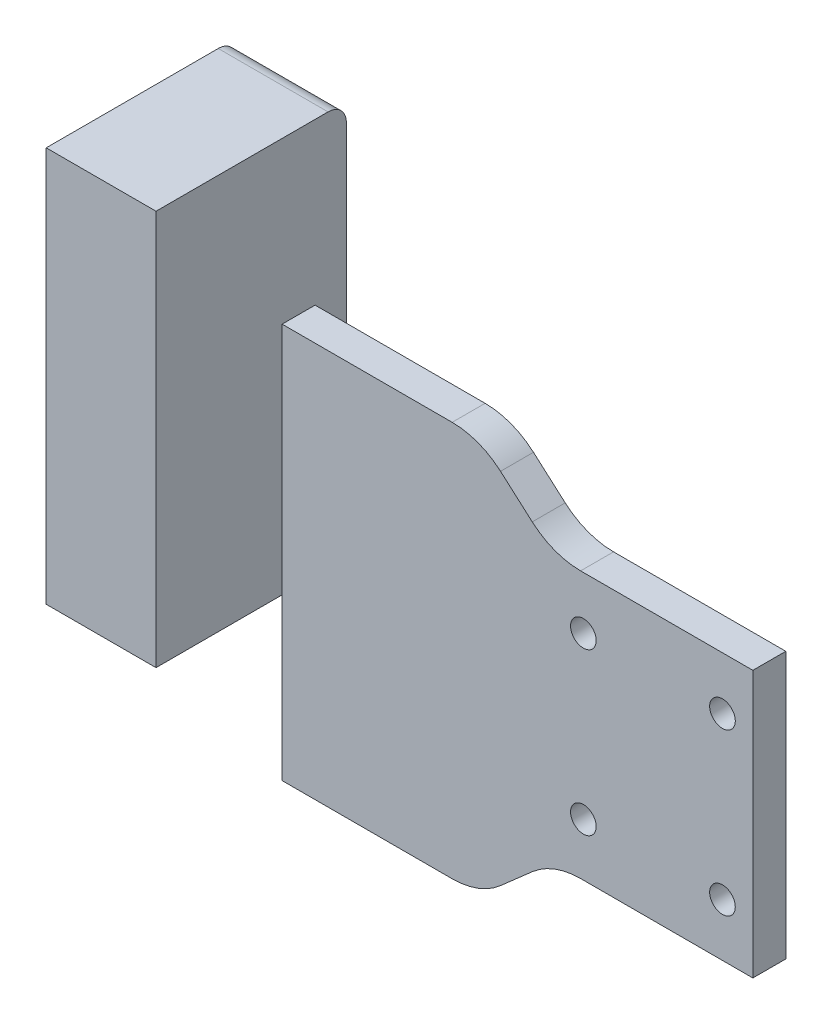
SolidWorks part; units mm, degrees
ref_plane "Front Plane" through (0, 0, 0) normal (0, 0, 1) x (1, 0, 0)
ref_plane "Top Plane" through (0, 0, 0) normal (0, 1, 0) x (1, 0, 0)
ref_plane "Right Plane" through (0, 0, 0) normal (1, 0, 0) x (0, 0, -1)
sketch "Sketch1" plane through (0, 0, 0) normal (0, 0, 1) x (1, 0, 0)
  line L0 (0, 18.2) -> (0, -18.2) construction
  line L1 (-13.65, -18.2) -> (13.65, -18.2)
  line L2 (-13.65, -18.2) -> (-13.65, 18.2) construction
  line L3 (-13.65, 18.2) -> (13.65, 18.2)
  line L4 (13.65, -18.2) -> (13.65, 18.2)
  line L5 (-13.65, -18.2) -> (13.65, 18.2) construction
  line L6 (-13.65, 18.2) -> (13.65, -18.2) construction
  line L7 (-13.65, 0) -> (13.65, 0) construction
  line L8 (-13.65, 0) -> (-113.65, 0) construction
  line L9 (-13.65, 18.2) -> (-23.65, 27)
  line L10 (-23.65, 27) -> (-50.65, 27)
  line L11 (-23.65, 27) -> (-23.65, -27) construction
  line L12 (-23.65, -27) -> (-50.65, -27)
  line L13 (-50.65, 27) -> (-50.65, -27)
  line L14 (-23.65, 27) -> (-50.65, -27) construction
  line L15 (-23.65, -27) -> (-50.65, 27) construction
  line L17 (-13.65, -18.2) -> (-23.65, -27)
  circle A0 centre (-9.5, 11) radius 1.75
  circle A1 centre (9.5, 11) radius 1.75
  circle A2 centre (-9.5, -11) radius 1.75
  circle A3 centre (9.5, -11) radius 1.75
  point P0 (0, 0)
  point P18 (-37.15, 0)
  dimension "D3" = 3.5
  dimension "D4" = 11
  dimension "D5" = 9.5
  dimension "D1" = 36.4
  dimension "D2" = 27.3
  dimension "D6" = 100
  dimension "D7" = 54
  dimension "D8" = 27
  dimension "D9" = 10
extrude "Boss-Extrude1" add sketch "Sketch1" along normal blind 4.5
sketch "Sketch2" plane through (0, 0, 0) normal (0, 0, 1) x (1, 0, 0)
  line L1 (-87.3764, 27.2465) -> (-72.3764, 27.2465)
  line L2 (-87.3764, 27.2465) -> (-87.3764, -26.7535)
  line L3 (-87.3764, -26.7535) -> (-72.3764, -26.7535)
  line L4 (-72.3764, 27.2465) -> (-72.3764, -26.7535)
  dimension "D1" = 15
  dimension "D2" = 54
extrude "Boss-Extrude2" add sketch "Sketch2" against normal blind 26
sketch "Sketch5" plane through (-72.3764, 0, 0) normal (1, 0, 0) x (0, 0, -1)
  line L2 (21, -21.5) -> (0, -21.5)
  line L3 (21, -21.5) -> (21, 21.5)
  line L4 (21, 21.5) -> (0, 21.5)
  line L5 (0, -21.5) -> (0, 21.5)
  line L6 (21, -21.5) -> (0, 21.5) construction
  line L7 (21, 21.5) -> (0, -21.5) construction
  point P3 (10.5, 0)
  point P8 (0, 21.5)
  point P9 (0, 21.5)
  dimension "D1" = 43
  dimension "D2" = 21
extrude "Cut-Extrude1" cut sketch "Sketch5" against normal up to surface (21.7264 mm away) rebuild error yes up to face at (-50.65, 0, 2.25)
sketch "Sketch6" plane through (-50.65, 0, 0) normal (-1, 0, 0) x (0, 0, 1)
  line L0 (-10.5, 21.5) -> (-10.5, -21.5) construction
  line L1 (0, 21.5) -> (-21, 21.5) construction
  line L2 (-21, -21.5) -> (0, -21.5) construction
  line L3 (-21, 0) -> (0, 0) construction
  line L4 (-21, 21.5) -> (-21, -21.5) construction
  line L5 (0, -27) -> (0, 27) construction
  circle A0 centre (-15.5, 24.75) radius 1.35
  circle A1 centre (-5.5, 24.75) radius 1.35
  circle A2 centre (-5.5, -24.75) radius 1.35
  circle A3 centre (-15.5, -24.75) radius 1.35
  point P20 (0, 0)
  dimension "D1" = 2.7
  dimension "D2" = 5
  dimension "D3" = 24.75
ref_plane "Plane1" through (0, 0, -10.5) normal (0, 0, -1) x (-1, 0, 0)
ref_plane "Plane2" through (0, 0, 0) normal (0, 1, 0) x (1, 0, 0)
extrude "Cut-Extrude2" cut sketch "Sketch6" against normal blind 12 rebuild error yes
sketch "Sketch8" plane through (-50.65, 0, 0) normal (-1, 0, 0) x (0, 0, 1)
  line L3 (-15.5, -21.5) -> (-5.5, -21.5)
  line L4 (-21, -21.5) -> (0, -21.5) construction
  line L5 (-15.5, -23.75) -> (-5.5, -23.75) construction
  line L6 (-15.5, -21.5) -> (-15.5, -23.75) construction
  line L7 (-5.5, -23.75) -> (-5.5, -21.5) construction
  arc A1 (-15.5, -21.5) -> (-5.5, -21.5) centre (-10.5, -17.0694) ccw
  point P5 (-10.5, -21.5)
  dimension "D1" = 10
  dimension "D2" = 2.25
extrude "Cut-Extrude3" cut sketch "Sketch8" against normal up to surface (21.7264 mm away) rebuild error yes up to face at (-72.3764, 0.2465, -13)
fillet "Fillet1" radius 10 4 edges at (-23.65, -27, 2.25) (-23.65, 27, 2.25) (-13.65, -18.2, 2.25) (-13.65, 18.2, 2.25)
fillet "Fillet3" radius 2.5 2 edges at (-79.8764, 27.2465, -26) (-79.8764, -26.7535, -26)
